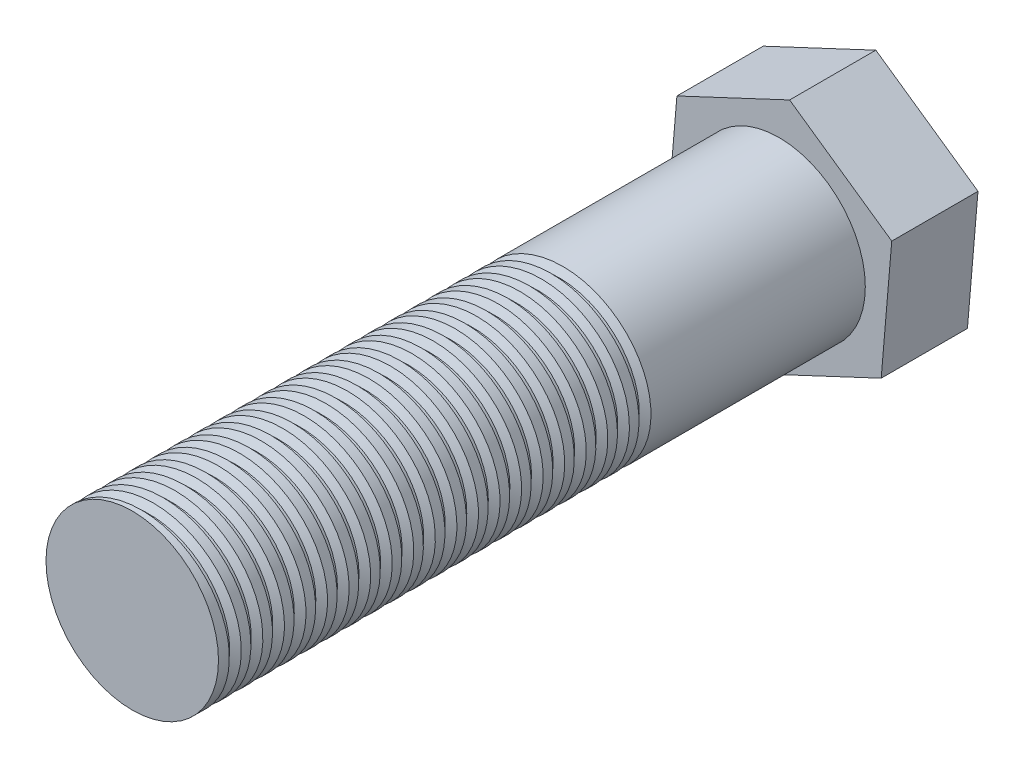
SolidWorks part; units mm, degrees
ref_plane "Front Plane" through (0, 0, 0) normal (0, 0, 1) x (1, 0, 0)
ref_plane "Top Plane" through (0, 0, 0) normal (0, 1, 0) x (1, 0, 0)
ref_plane "Right Plane" through (0, 0, 0) normal (1, 0, 0) x (0, 0, -1)
sketch "Sketch1" plane through (0, 0, 0) normal (0, 0, 1) x (1, 0, 0)
  line L1 (2.6134, 1.2263) -> (0.2447, 2.8764)
  line L2 (0.2447, 2.8764) -> (-2.3687, 1.6501)
  line L3 (-2.3687, 1.6501) -> (-2.6134, -1.2263)
  line L4 (-2.6134, -1.2263) -> (-0.2447, -2.8764)
  line L5 (-0.2447, -2.8764) -> (2.3687, -1.6501)
  line L6 (2.3687, -1.6501) -> (2.6134, 1.2263)
  circle A0 centre (0, 0) radius 2.5 construction
  dimension "D1" = 5
extrude "Boss-Extrude1" add sketch "Sketch1" along normal blind 2
sketch "Sketch2" plane through (0, 0, 2) normal (0, 0, 1) x (1, 0, 0)
  circle A0 centre (0, 0) radius 2
  dimension "D1" = 4
extrude "Boss-Extrude2" add sketch "Sketch2" along normal blind 15
thread "Thread1" pitch 0.3175 method cut profile "Thread Profile1" start angle 0, offset 0, length 10, pitch 0.5, diameter 4
ref_plane "Plane1" through (-2, 0, 17) normal (0, -1, 0) x (-1, 0, 0)
sketch "Thread Profile1" plane through (-2, 0, 17) normal (0, -1, 0) x (-1, 0, 0)
  line L0 (0, 0) -> (0, 0.3175) construction
  line L11 (0, 0) -> (0, 0.2778)
  line L12 (0, 0.2778) -> (-0.1719, 0.1786)
  line L13 (-0.1719, 0.1786) -> (-0.1719, 0.0992)
  line L15 (-0.1719, 0.0992) -> (0, 0)
  line L17 (-0.1719, 0.1389) -> (0, 0.1389) construction
  point P2 (0, 0)
  dimension "Pitch" = 0.3175
  dimension "Profile_Angle" = 60
  dimension "Profile_Land" = 0.0794
  dimension "Profile_Height" = 0.1719
